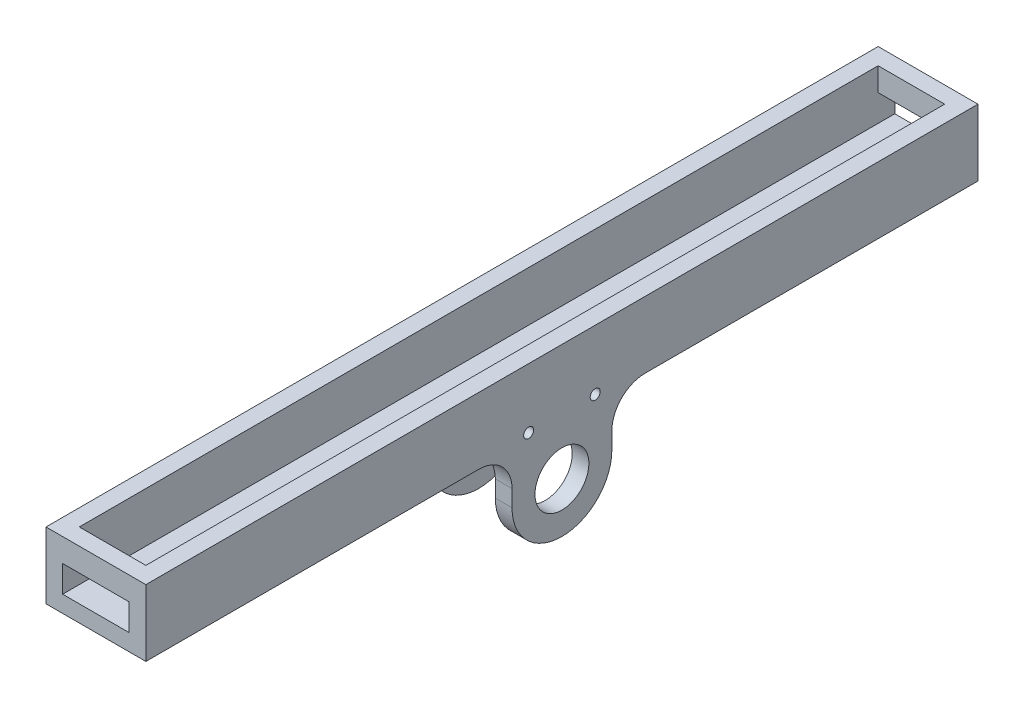
SolidWorks part; units mm, degrees
ref_plane "Front Plane" through (0, 0, 0) normal (0, 0, 1) x (1, 0, 0)
ref_plane "Top Plane" through (0, 0, 0) normal (0, 1, 0) x (1, 0, 0)
ref_plane "Right Plane" through (0, 0, 0) normal (1, 0, 0) x (0, 0, -1)
sketch "Sketch1" plane through (0, 0, 0) normal (0, 0, 1) x (1, 0, 0)
  line L0 (25, 20) -> (30, 20)
  line L1 (0, 0) -> (30, 0)
  line L2 (0, 0) -> (0, 20)
  line L3 (0, 20) -> (5, 20)
  line L4 (30, 0) -> (30, 20)
  line L6 (5, 20) -> (5, 5)
  line L7 (5, 5) -> (25, 5)
  line L8 (25, 20) -> (25, 5)
  dimension "D1" = 20
  dimension "D2" = 5
  dimension "D3" = 5
  dimension "D4" = 5
  dimension "D5" = 15
extrude "Boss-Extrude1" add sketch "Sketch1" along normal blind 250
sketch "Sketch2" plane through (30, 0, 0) normal (1, 0, 0) x (0, 0, -1)
  line L5 (-250, 0) -> (0, 0) construction
  line L6 (-140, -15) -> (-140, -10)
  line L7 (-110, -15) -> (-110, -10)
  line L10 (-150, 0) -> (-100, 0)
  circle A0 centre (-125, -15) radius 8.1
  arc A1 (-140, -15) -> (-110, -15) centre (-125, -15) ccw
  arc A2 (-110, -10) -> (-100, 0) centre (-100, -10) cw
  arc A3 (-140, -10) -> (-150, 0) centre (-150, -10) ccw
  point P4 (-125, 0)
  point P11 (-85, 0)
  point P14 (-115, 0)
  dimension "D2" = 16.2
  dimension "D3" = 10
  dimension "D4" = 15
  dimension "D1" = 15
  dimension "D5" = 50
sketch "Sketch3" plane through (30, 0, 0) normal (1, 0, 0) x (0, 0, -1)
  line L0 (-250, 0) -> (0, 0) construction
  line L1 (-225, 0) -> (-215, 0)
  line L2 (-225, 0) -> (-225, -10)
  line L3 (-225, -10) -> (-215, -10)
  line L4 (-215, 0) -> (-215, -10)
  line L5 (-250, 0) -> (-250, 20) construction
  circle A0 centre (-220, -5) radius 1.75
  dimension "D2" = 3.5
  dimension "D1" = 5
  dimension "D3" = 5
  dimension "D4" = 10
  dimension "D5" = 10
  dimension "D6" = 25
extrude "Boss-Extrude3" add sketch "Sketch3" along normal blind 7 from offset 17.1 offset against normal yes
fillet "Fillet1" radius 5 2 edges at (16.4, -10, 215) (16.4, -10, 225)
sketch "Sketch5" plane through (0, 5, 0) normal (0, 1, 0) x (1, 0, 0)
  line L0 (25, -250) -> (5, -250) construction
  line L1 (5, -125) -> (25, -125) construction
  line L2 (5, -250) -> (5, 0) construction
  line L3 (25, -250) -> (25, 0) construction
  circle A0 centre (15, -230) radius 1.5
  circle A1 centre (15, -210) radius 1.5
  circle A2 centre (15, -40) radius 1.5
  circle A3 centre (15, -20) radius 1.5
  point P8 (15, -250)
  dimension "D3" = 3
  dimension "D1" = 20
  dimension "D2" = 20
extrude "Cut-Extrude1" cut sketch "Sketch5" against normal blind 7
sketch "Sketch6" plane through (0, 20, 0) normal (0, 1, 0) x (1, 0, 0)
  line L0 (25, -250) -> (25, 0) construction
  line L1 (5, 0) -> (25, 0)
  line L2 (5, 0) -> (5, -5)
  line L3 (5, -5) -> (25, -5)
  line L4 (25, 0) -> (25, -5)
  line L5 (25, -250) -> (25, 0) construction
  line L6 (5, -250) -> (25, -250)
  line L7 (5, -250) -> (5, -245)
  line L8 (5, -245) -> (25, -245)
  line L9 (25, -250) -> (25, -245)
  dimension "D1" = 5
  dimension "D2" = 5
extrude "Boss-Extrude4" add sketch "Sketch6" against normal blind 7
extrude "Boss-Extrude5" add sketch "Sketch2" against normal blind 5
extrude "Boss-Extrude6" add sketch "Sketch2<3>" along normal blind 5 from surface starting at face at (0, 10, 125)
sketch "Sketch2<3>" plane through (30, 0, 0) normal (1, 0, 0) x (0, 0, -1) same geometry as "Sketch2"
sketch "Sketch7" plane through (0, 0, 0) normal (-1, 0, 0) x (0, 0, 1)
  line L0 (250, 20) -> (0, 20) construction
  circle A0 centre (115, 2) radius 1.5
  circle A1 centre (135, 2) radius 1.5
  circle A2 centre (125, -15) radius 8.1 construction
  dimension "D1" = 3
  dimension "D2" = 3
  dimension "D3" = 20
  dimension "D4" = 10
  dimension "D5" = 18
extrude "Cut-Extrude2" cut sketch "Sketch7" against normal through all
